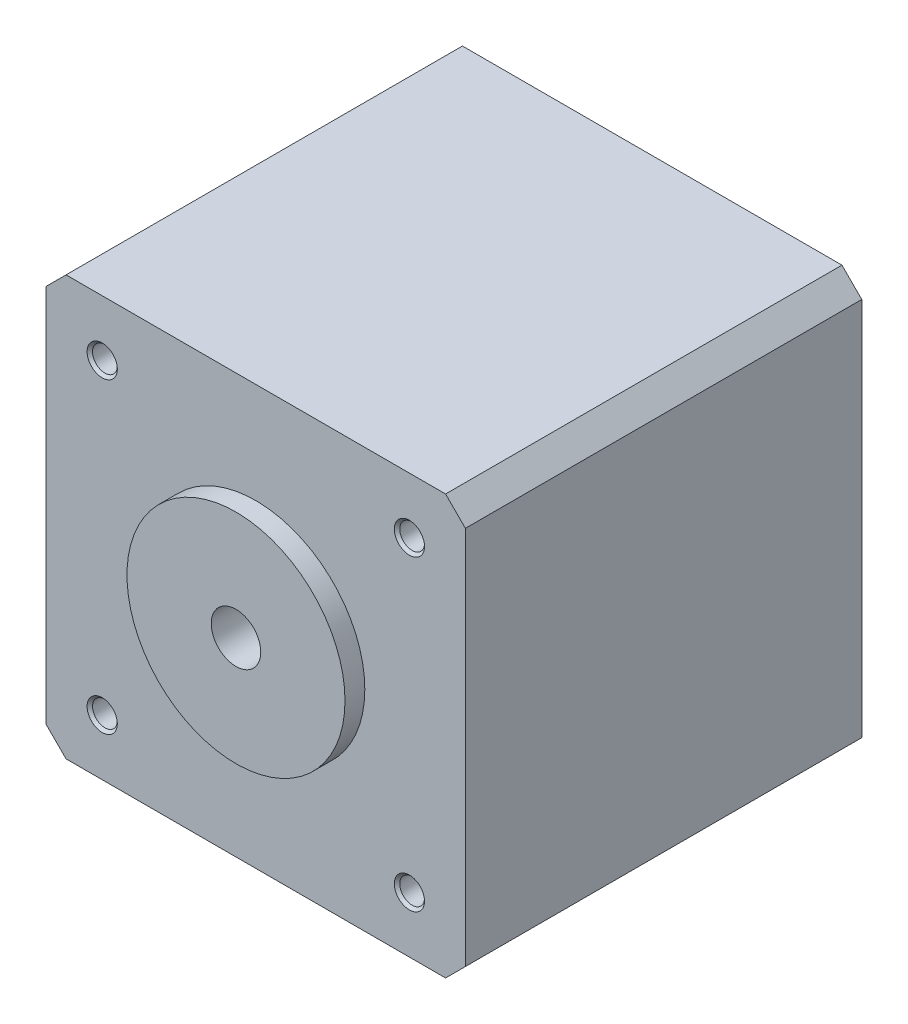
SolidWorks part; units mm, degrees
ref_plane "정면" through (0, 0, 0) normal (0, 0, 1) x (1, 0, 0)
ref_plane "윗면" through (0, 0, 0) normal (0, 1, 0) x (1, 0, 0)
ref_plane "우측면" through (0, 0, 0) normal (1, 0, 0) x (0, 0, -1)
sketch "스케치1" plane through (0, 0, 0) normal (0, 0, 1) x (1, 0, 0)
  line L1 (-21.15, 21.15) -> (21.15, 21.15)
  line L2 (-21.15, 21.15) -> (-21.15, -21.15)
  line L3 (-21.15, -21.15) -> (21.15, -21.15)
  line L4 (21.15, 21.15) -> (21.15, -21.15)
  line L5 (-21.15, 21.15) -> (21.15, -21.15) construction
  line L6 (-21.15, -21.15) -> (21.15, 21.15) construction
  point P0 (0, 0)
  dimension "D1" = 42.3
  dimension "D2" = 42.3
extrude "보스-돌출1" add sketch "스케치1" along normal blind 40
hole_wizard "M3 나사 구멍1" positions "스케치3" profile "스케치5" tap size "M3" standard "KS"
sketch "스케치3" plane through (0, 0, 40) normal (0, 0, 1) x (1, 0, 0)
  line L1 (-21.15, 21.15) -> (-21.15, -21.15) construction
  line L2 (21.15, 21.15) -> (-21.15, 21.15) construction
  point P0 (-15.5, 15.5)
  point P2 (15.5, 15.5)
  point P4 (15.5, -15.5)
  point P6 (-15.5, -15.5)
  dimension "D1" = 31
  dimension "D2" = 31
  dimension "D3" = 5.65
  dimension "D4" = 5.65
sketch "스케치5" plane through (-15.5, 15.5, 40) normal (1, 0, 0) x (0, -1, 0)
  line L0 (0, 0) -> (0, 9.2511)
  line L1 (0, 9.2511) -> (1.25, 8.5)
  line L2 (1.25, 8.5) -> (1.25, 0.275)
  line L3 (1.25, 0.275) -> (1.525, 0)
  line L5 (1.525, 0) -> (0, 0)
  line L6 (-1.25, 0.275) -> (-1.525, 0) construction
  line L10 (0, 9.2511) -> (-1.25, 8.5) construction
  line L11 (0, -6.35) -> (0, 107.95) construction
  dimension "탭 드릴 지름" = 2.5
  dimension "탭 드릴 깊이" = 8.5
  dimension "표면 카운터싱크 지름" = 3.05
  dimension "표면 카운터싱크 각도" = 90
  dimension "드릴 각도" = 118
cosmetic thread "구멍 나사산1" parameters "D1"=6, "D2"=3
cosmetic thread "구멍 나사산2" parameters "D1"=6, "D2"=3
cosmetic thread "구멍 나사산3" parameters "D1"=6, "D2"=3
cosmetic thread "구멍 나사산4" parameters "D1"=6, "D2"=3
sketch "스케치6" plane through (0, 0, 40) normal (0, 0, 1) x (1, 0, 0)
  circle A0 centre (0, 0) radius 11
  dimension "D1" = 22
extrude "보스-돌출2" add sketch "스케치6" along normal blind 2
ref_plane "평면1" through (0, 0, 20) normal (0, 0, -1) x (-1, 0, 0)
mirror "대칭 복사1" about plane through (0, 0, 20) normal (0, 0, -1) of "보스-돌출2"
sketch "스케치7" plane through (0, 0, 42) normal (0, 0, 1) x (1, 0, 0)
  circle A0 centre (0, 0) radius 2.5
  dimension "D1" = 5
extrude "컷-돌출1" cut sketch "스케치7" against normal through all
chamfer "모따기1" distance 2 angle 45 4 edges at (-21.15, -21.15, 20) (21.15, -21.15, 20) (21.15, 21.15, 20) (-21.15, 21.15, 20)
